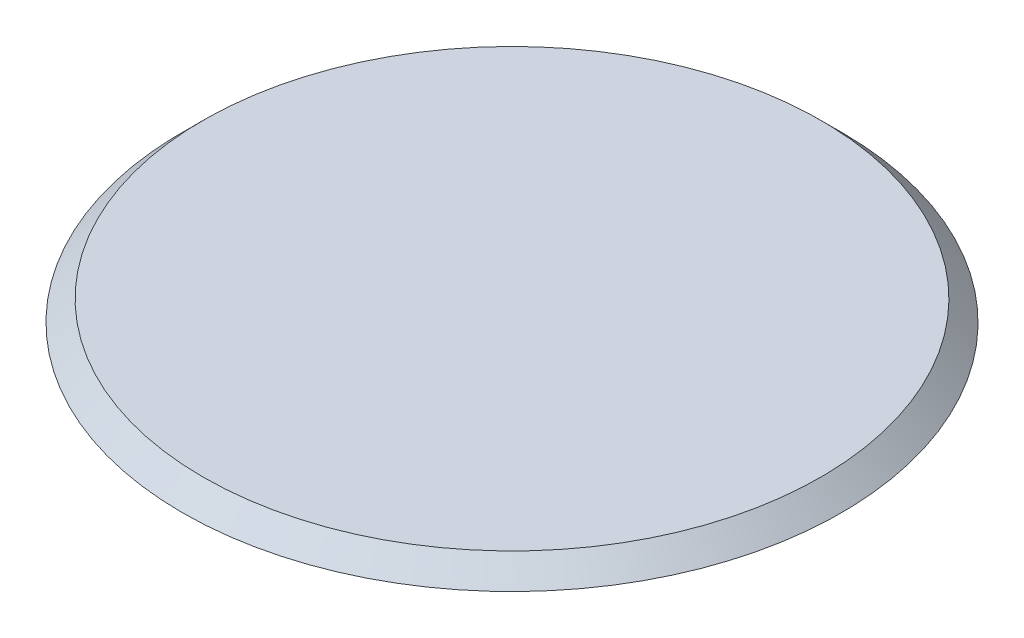
SolidWorks part; units mm, degrees
ref_plane "Front Plane" through (0, 0, 0) normal (0, 0, 1) x (1, 0, 0)
ref_plane "Top Plane" through (0, 0, 0) normal (0, 1, 0) x (1, 0, 0)
ref_plane "Right Plane" through (0, 0, 0) normal (1, 0, 0) x (0, 0, -1)
sketch "Sketch1" plane through (0, 0, 0) normal (0, 0, 1) x (1, 0, 0)
  line L0 (0, 0) -> (16, 0)
  line L1 (16, 0) -> (15, 1)
  line L2 (15, 1) -> (0, 1)
  line L3 (0, 1) -> (0, 0)
  dimension "D1" = 16
  dimension "D2" = 45
  dimension "D3" = 1
  dimension "D4" = 15
revolve "Foot Revolve" add sketch "Sketch1" angle 360 about L3
shell "Foot Shell" thickness 0.5 removed face at (0, 0, 16)
fillet "Foot Fillet" radius 16 1 edges at (0, 0.5, -14.7929)
